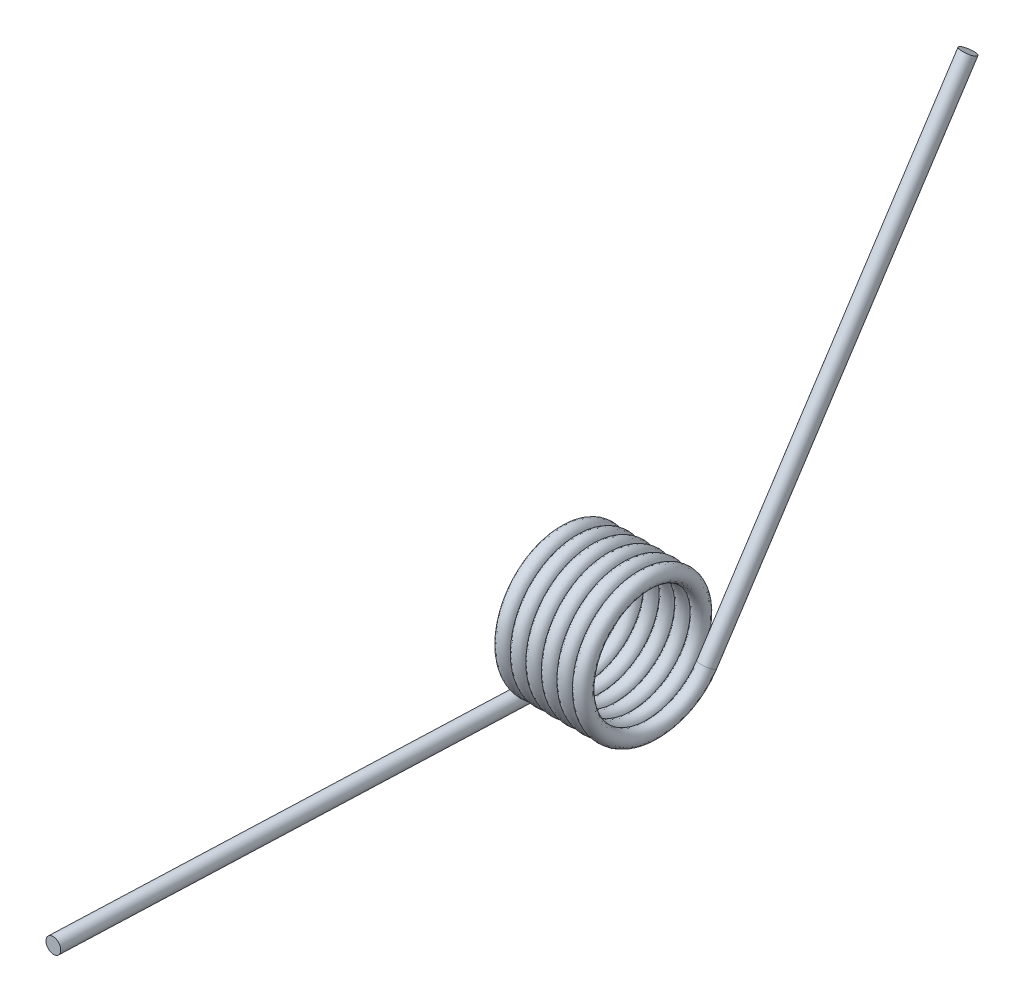
SolidWorks part; units mm, degrees
ref_plane "Front" through (0, 0, 0) normal (0, 0, 1) x (1, 0, 0)
ref_plane "Top" through (0, 0, 0) normal (0, 1, 0) x (1, 0, 0)
ref_plane "Right" through (0, 0, 0) normal (1, 0, 0) x (0, 0, -1)
sketch "Sketch1" plane through (0, 0, 0) normal (1, 0, 0) x (0, 0, -1)
  line L0 (0, -8.6487) -> (0, -11.0617) construction
  line L1 (9.5797, -5.5309) -> (47.6797, 60.4603) construction
  line L2 (0, -11.0617) -> (-76.2, -11.0617) construction
  line L3 (0, 0) -> (11.0617, 0) construction
  line L4 (0, 0) -> (9.5797, -5.5309) construction
  line L5 (-76.2, -11.0617) -> (-76.2, -8.6487) construction
  line L6 (-76.2, -8.6487) -> (0, -8.6487) construction
  line L7 (47.6797, 60.4603) -> (45.59, 61.6668) construction
  line L8 (45.59, 61.6668) -> (7.49, -4.3244) construction
  circle A0 centre (0, 0) radius 11.0617 construction
  circle A1 centre (0, 0) radius 7.9375 construction
  circle A2 centre (0, 0) radius 9.8552 construction
  point P7 (0, -9.8552)
  point P10 (0, 11.0617)
  dimension "OD" = 22.1234
  dimension "For Shaft Diameter" = 15.875
  dimension "Wire Diameter" = 2.413
  dimension "Leg Length" = 76.2
  dimension "Deflection Angle" = 120
sketch "Sketch2" plane through (0, 0, 0) normal (1, 0, 0) x (0, 0, -1)
  circle A0 centre (0, 0) radius 9.8552 construction
  circle A2 centre (0, 0) radius 9.8552
curve "Helix/Spiral1" pitch 2.4384 height 15.0368 radius 9.8552 centre (0, 0, 0) axis (1, 0, 0) start towards (0, 0, -1)
ref_plane "Plane1" through (0, -9.8552, 0) normal (0.0393, 0, -0.9992) x (0.999, -0.0232, 0.0393)
sketch "Sketch3" plane through (0, -9.8552, 0) normal (0.0393, 0, -0.9992) x (0.999, -0.0232, 0.0393)
  circle A0 centre (0, 0) radius 1.2065
  dimension "D1" = 2.413
sweep "Sweep1" add profiles "Sketch3" path "Helix/Spiral1"
sketch "Sketch4" plane through (0, 0, 0) normal (-0.0393, 0, 0.9992) x (-0.999, 0.0232, -0.0393)
  circle A1 centre (-0.229, 9.8525) radius 1.2065
  circle A2 centre (-0.229, 9.8525) radius 1.2065
  dimension "D1" = 0
extrude "Extrude1" add sketch "Sketch4" along normal blind 76.2
sketch "Sketch5" plane through (0.0233, 0.512, -0.2956) normal (0.0393, 0.8654, -0.4996) x (0.9982, -0.0569, -0.02)
  circle A1 centre (15.4605, 9.1571) radius 1.2065
  circle A2 centre (15.4605, 9.1571) radius 1.2065
  dimension "D1" = 0
extrude "Extrude2" add sketch "Sketch5" along normal blind 76.2
sketch "Sketch6" plane through (0, 0, 0) normal (1, 0, 0) x (0, 0, -1)
  circle A2 centre (0, 0) radius 8.6487 construction
equation "\"D4@Helix/Spiral1\" = \"Wire Diameter@Sketch1\" + .001"
equation "\"D1@Sketch3\"=\"Wire Diameter@Sketch1\""
equation "\"D1@Extrude2\"=\"Leg Length@Sketch1\""
equation "\"Leg Length@Extrude1\"=\"Leg Length@Sketch1\""
